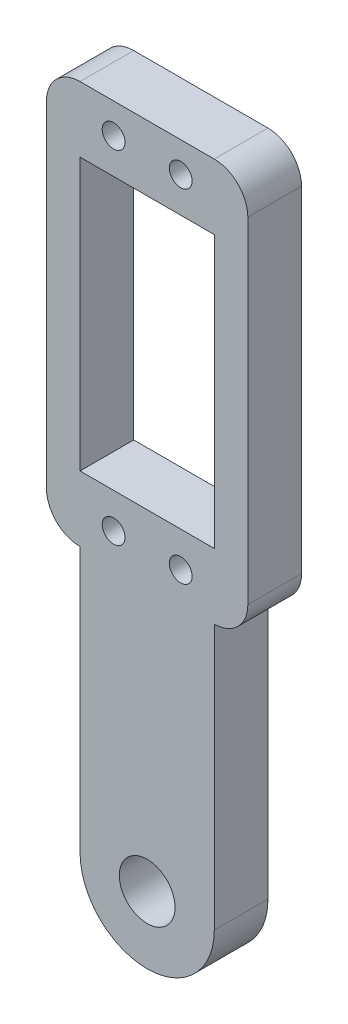
SolidWorks part; units mm, degrees
ref_plane "Спереди" through (0, 0, 0) normal (0, 0, 1) x (1, 0, 0)
ref_plane "Сверху" through (0, 0, 0) normal (0, 1, 0) x (1, 0, 0)
ref_plane "Справа" through (0, 0, 0) normal (1, 0, 0) x (0, 0, -1)
sketch "Эскиз1" plane through (0, 0, 0) normal (0, 0, 1) x (1, 0, 0)
  line L0 (0, 0) -> (0, 80) construction
  line L1 (-10, 69.5) -> (10, 69.5) construction
  line L2 (-10, 89.75) -> (10, 89.75)
  line L3 (-10, 89.75) -> (-10, 49.25)
  line L4 (-10, 49.25) -> (10, 49.25)
  line L5 (10, 89.75) -> (10, 49.25)
  line L6 (-10, 0) -> (-10, 39.5)
  line L7 (-15, 99.5) -> (15, 99.5)
  line L8 (-15, 99.5) -> (-15, 39.5)
  line L9 (-15, 39.5) -> (15, 39.5)
  line L10 (15, 99.5) -> (15, 39.5)
  line L11 (10, 0) -> (10, 39.5)
  circle A0 centre (0, 0) radius 4.15
  circle A1 centre (0, 0) radius 10
  circle A2 centre (0, 80) radius 5
  circle A3 centre (-5, 95) radius 1.7
  circle A4 centre (5, 95) radius 1.7
  circle A5 centre (-5, 44) radius 1.7
  circle A6 centre (5, 44) radius 1.7
  dimension "D1" = 8.3
  dimension "D2" = 20
  dimension "D6" = 10
  dimension "D9" = 3.4
  dimension "D10" = 15
  dimension "D3" = 80
  dimension "D4" = 20
  dimension "D5" = 40.5
  dimension "D7" = 9.75
  dimension "D8" = 80
  dimension "D11" = 10
  dimension "D12" = 30
  dimension "D13" = 60
extrude "Бобышка-Вытянуть1" add sketch "Эскиз1" along normal blind 8 contours L10 L7 L8 L9 A5 A4 A3 L2 L5 L4 L3 A6 | A1 A0 | A1 L11 L9 L6 region at (0, 23.5983, 0) region at (0, 9.7172, 0) region at (-12.5, 40.1708, 0)
fillet "Скругление1" radius 5 4 edges at (15, 39.5, 4) (-15, 39.5, 4) (-15, 99.5, 4) (15, 99.5, 4)
